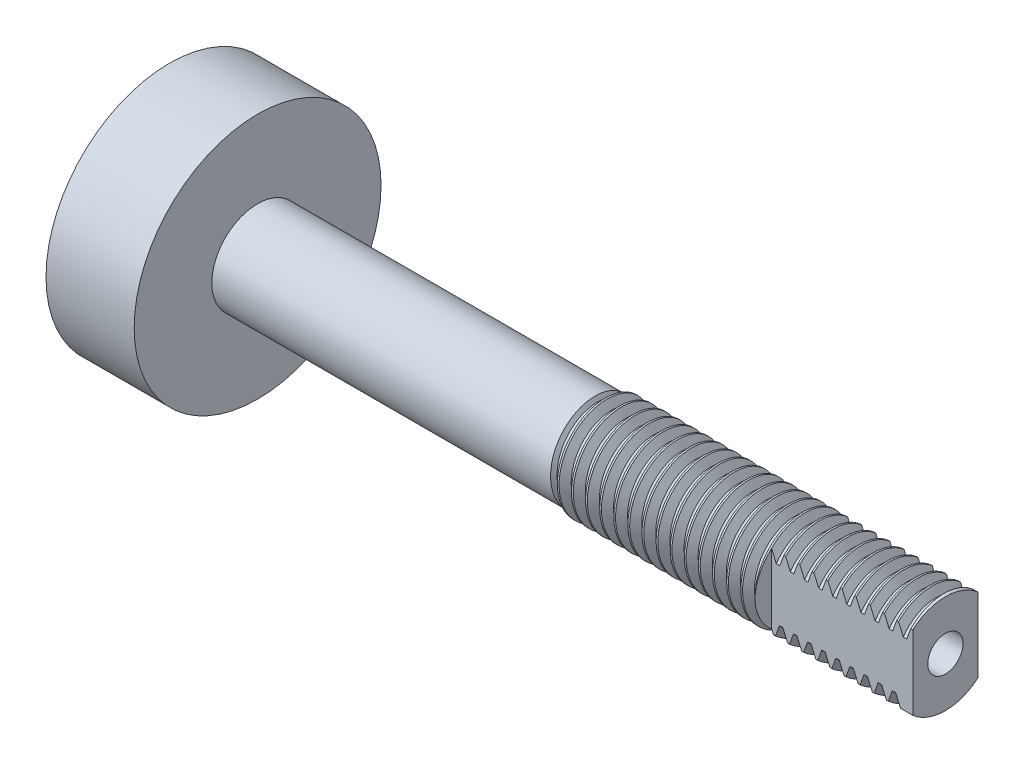
SolidWorks part; units mm, degrees
ref_plane "Front Plane" through (0, 0, 0) normal (0, 0, 1) x (1, 0, 0)
ref_plane "Top Plane" through (0, 0, 0) normal (0, 1, 0) x (1, 0, 0)
ref_plane "Right Plane" through (0, 0, 0) normal (1, 0, 0) x (0, 0, -1)
sketch "Sketch1" plane through (0, 0, 0) normal (1, 0, 0) x (0, 0, -1)
  circle A0 centre (0, 0) radius 2.8
  dimension "D1" = 5.6
extrude "Boss-Extrude1" add sketch "Sketch1" along normal mid plane 39
sketch "Sketch2" plane through (19.5, 0, 0) normal (1, 0, 0) x (0, 0, -1)
  line L0 (-1.85, 2.1018) -> (-1.85, -2.1018)
  line L1 (1.85, 2.1018) -> (1.85, -2.1018)
  arc A0 (-1.85, 2.1018) -> (-1.85, -2.1018) centre (0, 0) ccw
  arc A1 (1.85, -2.1018) -> (1.85, 2.1018) centre (0, 0) ccw
  dimension "D3" = 5.6
  dimension "D1" = 3.7
  dimension "D2" = 1.85
extrude "Cut-Extrude1" cut sketch "Sketch2" against normal blind 8
sketch "Sketch3" plane through (19.5, 0, 0) normal (1, 0, 0) x (0, 0, -1)
  circle A0 centre (0, 0) radius 1
  dimension "D1" = 2
extrude "Cut-Extrude2" cut sketch "Sketch3" against normal blind 6
ref_plane "Plane1" through (-19.5, 0, 0) normal (-1, 0, 0) x (0, 0, 1)
sketch "Sketch5" plane through (-19.5, 0, 0) normal (-1, 0, 0) x (0, 0, 1)
  circle A0 centre (0, 0) radius 7
  dimension "D1" = 14
extrude "Boss-Extrude2" add sketch "Sketch5" along normal blind 5 contours A0
ref_plane "Plane3" through (0, 0, 0) normal (1, 0, 0) x (0, 0, -1)
sketch "Sketch7" plane through (0, 0, 0) normal (1, 0, 0) x (0, 0, -1)
  circle A0 centre (0, 0) radius 2.6
  circle A1 centre (0, 0) radius 2.9
  dimension "D1" = 5.2
  dimension "D2" = 5.8
extrude "Cut-Extrude3" cut sketch "Sketch7" against normal blind 19.5
thread "Thread1" pitch 0.8 method cut profile "Thread Profile1" start angle 0, offset 0, length 0, pitch 0.8, diameter 5.6
ref_plane "Plane4" through (19.5, 0, 2.8) normal (0, -1, 0) x (0, 0, 1)
sketch "Thread Profile1" plane through (19.5, 0, 2.8) normal (0, -1, 0) x (0, 0, 1)
  line L0 (0, 0) -> (0, 0.8) construction
  line L11 (0, 0) -> (0, 0.7)
  line L12 (0, 0.7) -> (-0.433, 0.45)
  line L13 (-0.433, 0.45) -> (-0.433, 0.25)
  line L15 (-0.433, 0.25) -> (0, 0)
  line L17 (-0.433, 0.35) -> (0, 0.35) construction
  point P2 (0, 0)
  dimension "Pitch" = 0.8
  dimension "Profile_Angle" = 60
  dimension "Profile_Land" = 0.2
  dimension "Profile_Height" = 0.433
equation "\"shaftdiameter\"= 5.6"
equation "\"D1@Sketch1\"=\"shaftdiameter\""
equation "\"D3@Sketch2\"=\"shaftdiameter\""
equation "\"motor_cut\"= 8"
equation "\"D1@Cut-Extrude1\"=\"motor_cut\""
equation "\"D1@Sketch7\"=5.2"
equation "\"D2@Sketch7\"=\"shaftdiameter\"+.2"
